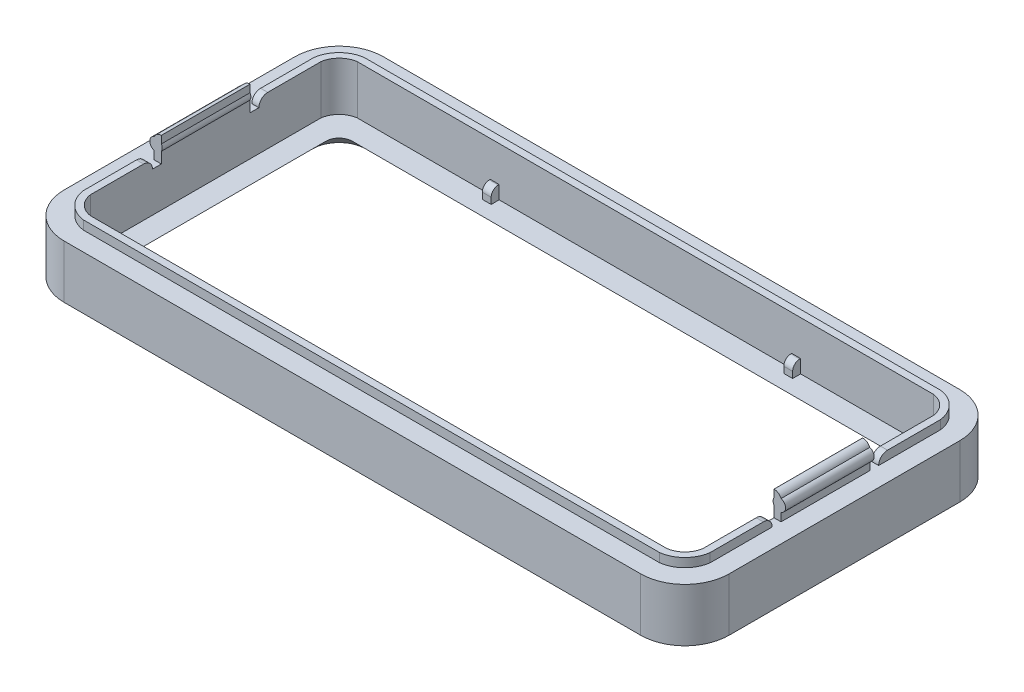
SolidWorks part; units mm, degrees
ref_plane "前视基准面" through (0, 0, 0) normal (0, 0, 1) x (1, 0, 0)
ref_plane "上视基准面" through (0, 0, 0) normal (0, 1, 0) x (1, 0, 0)
ref_plane "右视基准面" through (0, 0, 0) normal (1, 0, 0) x (0, 0, -1)
sketch "zero" plane through (0, 0, 0) normal (0, 1, 0) x (1, 0, 0)
  line L1 (-29.5, 15) -> (29.5, 15)
  line L2 (-32.5, 12) -> (-32.5, -12)
  line L3 (-29.5, -15) -> (29.5, -15)
  line L4 (32.5, 12) -> (32.5, -12)
  line L5 (-32.5, 15) -> (32.5, -15) construction
  line L6 (-32.5, -15) -> (32.5, 15) construction
  line L7 (-25.7, -15) -> (-14.5, -15)
  line L8 (-25.7, -15) -> (-25.7, -9.6569)
  line L9 (-25.7, -9.6569) -> (-14.5, -9.6569)
  line L10 (-14.5, -15) -> (-14.5, -9.6569)
  line L11 (5.2, -15) -> (12.7, -15)
  line L12 (5.2, -15) -> (5.2, -11)
  line L13 (5.2, -11) -> (12.7, -11)
  line L14 (12.7, -15) -> (12.7, -11)
  line L15 (17.8, -15) -> (25.3, -15)
  line L16 (17.8, -15) -> (17.8, -11)
  line L17 (17.8, -11) -> (25.3, -11)
  line L18 (25.3, -15) -> (25.3, -11)
  line L19 (-32.5, 7.7) -> (-19.5, 7.7)
  line L20 (-32.5, 7.7) -> (-32.5, -4.3)
  line L21 (-32.5, -4.3) -> (-19.5, -4.3)
  line L22 (-19.5, 7.7) -> (-19.5, -4.3)
  line L23 (-25.5, 14) -> (25.5, 14)
  line L24 (-25.5, 14) -> (-25.5, 8.8)
  line L25 (-25.5, 8.8) -> (25.5, 8.8)
  line L26 (25.5, 14) -> (25.5, 8.8)
  line L27 (-19.5, 7.2329) -> (-35.5, 7.2329)
  line L28 (-19.5, 7.2329) -> (-19.5, -3.7671)
  line L29 (-19.5, -3.7671) -> (-35.5, -3.7671)
  line L30 (-35.5, 7.2329) -> (-35.5, -3.7671)
  arc A0 (29.5, -15) -> (32.5, -12) centre (29.5, -12) ccw
  arc A1 (29.5, 15) -> (32.5, 12) centre (29.5, 12) cw
  arc A2 (-32.5, -12) -> (-29.5, -15) centre (-29.5, -12) ccw
  arc A3 (-29.5, 15) -> (-32.5, 12) centre (-29.5, 12) ccw
  circle A4 centre (-29, 11.4) radius 3
  circle A5 centre (-29, -11.5) radius 3
  circle A6 centre (29, 11.4) radius 3
  circle A7 centre (29, -11.5) radius 3
  circle A8 centre (-29, 11.4) radius 1.375
  circle A9 centre (-29, -11.5) radius 1.375
  circle A10 centre (29, -11.5) radius 1.375
  circle A11 centre (29, 11.4) radius 1.375
  point P0 (0, 0)
  dimension "D3" = 3
  dimension "D4" = 6
  dimension "D9" = 2.75
  dimension "D1" = 65
  dimension "D2" = 30
  dimension "D5" = 3.6
  dimension "D6" = 3.5
  dimension "D7" = 3.5
  dimension "D8" = 3.5
  dimension "D10" = 12
  dimension "D11" = 7.3
  dimension "D12" = 13
  dimension "D13" = 11.2
  dimension "D14" = 6.8
  dimension "D15" = 19.7
  dimension "D16" = 7.5
  dimension "D17" = 7.5
  dimension "D18" = 5.1
  dimension "D19" = 4
  dimension "D20" = 5.2
  dimension "D21" = 7
  dimension "D22" = 7
  dimension "D23" = 1
  dimension "D24" = 11
  dimension "D25" = 16
sketch "sugar" plane through (0, 0, 0) normal (0, 1, 0) x (1, 0, 0)
  line L1 (-29.5, 15) -> (29.5, 15)
  line L2 (-32.5, 12) -> (-32.5, -12)
  line L3 (-29.5, -15) -> (29.5, -15)
  line L4 (32.5, 12) -> (32.5, -12)
  line L5 (-32.5, 15) -> (32.5, -15) construction
  line L6 (-32.5, -15) -> (32.5, 15) construction
  line L7 (23.5, -11.5) -> (19.5, -11.5)
  line L8 (23.5, -11.5) -> (23.5, -13.9082)
  line L9 (23.5, -13.9082) -> (19.5, -13.9082)
  line L10 (19.5, -11.5) -> (19.5, -13.9082)
  line L11 (16, -11.0071) -> (8.5, -11.0071)
  line L12 (16, -11.0071) -> (16, -15)
  line L13 (16, -15) -> (8.5, -15)
  line L14 (8.5, -11.0071) -> (8.5, -15)
  line L15 (20.5, -13.9082) -> (22.5, -13.9082)
  line L16 (20.5, -13.9082) -> (20.5, -14.8173)
  line L17 (20.5, -14.8173) -> (22.5, -14.8173)
  line L18 (22.5, -13.9082) -> (22.5, -14.8173)
  arc A0 (29.5, 15) -> (32.5, 12) centre (29.5, 12) cw
  arc A1 (29.5, -15) -> (32.5, -12) centre (29.5, -12) ccw
  arc A2 (-32.5, -12) -> (-29.5, -15) centre (-29.5, -12) ccw
  arc A3 (-29.5, 15) -> (-32.5, 12) centre (-29.5, 12) ccw
  circle A4 centre (-29, 11.4) radius 3
  circle A5 centre (-29, 11.4) radius 1.375
  circle A6 centre (-29, -11.5) radius 3
  circle A7 centre (-29, -11.5) radius 1.375
  circle A8 centre (29, 11.4) radius 3
  circle A9 centre (29, 11.4) radius 1.375
  circle A10 centre (29, -11.5) radius 3
  circle A11 centre (29, -11.5) radius 1.375
  dimension "D3" = 3
  dimension "D1" = 65
  dimension "D2" = 30
  dimension "D4" = 9
  dimension "D5" = 4
  dimension "D6" = 3.5
  dimension "D7" = 7.5
  dimension "D8" = 2
  dimension "D9" = 1
sketch "case" plane through (0, 0, 0) normal (0, 1, 0) x (1, 0, 0)
  line L1 (-34.0422, 18) -> (30.9578, 18)
  line L2 (-39.0422, 13) -> (-39.0422, -13)
  line L3 (-34.0422, -18) -> (30.9578, -18)
  line L4 (35.9578, 13) -> (35.9578, -13)
  line L5 (-39.0422, 18) -> (35.9578, -18) construction
  line L6 (-39.0422, -18) -> (35.9578, 18) construction
  arc A0 (-39.0422, -13) -> (-34.0422, -18) centre (-34.0422, -13) ccw
  arc A1 (30.9578, -18) -> (35.9578, -13) centre (30.9578, -13) ccw
  arc A2 (30.9578, 18) -> (35.9578, 13) centre (30.9578, 13) cw
  arc A3 (-34.0422, 18) -> (-39.0422, 13) centre (-34.0422, 13) ccw
  point P0 (-1.5422, 0)
  point P3 (-1.5422, 0)
  dimension "D3" = 5
  dimension "D1" = 75
  dimension "D2" = 36
extrude "凸台-拉伸2" add sketch "case" along normal blind 6
sketch "草图2" plane through (0, 0, 0) normal (0, 1, 0) x (1, 0, 0)
  line L4 (-34.0422, -15.05) -> (30.9578, -15.05)
  line L5 (33.0078, -13) -> (33.0078, 13)
  line L6 (30.9578, 15.05) -> (-34.0422, 15.05)
  line L7 (-36.0922, 13) -> (-36.0922, -13)
  line L12 (33.8078, -13) -> (33.8078, 13)
  line L13 (30.9578, 15.85) -> (-34.0422, 15.85)
  line L14 (-36.8922, 13) -> (-36.8922, -13)
  line L15 (-34.0422, -15.85) -> (30.9578, -15.85)
  arc A4 (30.9578, -15.05) -> (33.0078, -13) centre (30.6303, -12.6725) ccw
  arc A5 (33.0078, 13) -> (30.9578, 15.05) centre (30.6303, 12.6725) ccw
  arc A6 (-34.0422, 15.05) -> (-36.0922, 13) centre (-33.7147, 12.6725) ccw
  arc A7 (-36.0922, -13) -> (-34.0422, -15.05) centre (-33.7147, -12.6725) ccw
  arc A12 (30.9578, -15.85) -> (33.8078, -13) centre (30.535, -12.5772) ccw
  arc A13 (33.8078, 13) -> (30.9578, 15.85) centre (30.535, 12.5772) ccw
  arc A14 (-34.0422, 15.85) -> (-36.8922, 13) centre (-33.6194, 12.5772) ccw
  arc A15 (-36.8922, -13) -> (-34.0422, -15.85) centre (-33.6194, -12.5772) ccw
ref_plane "基准面1" through (0, 6, 0) normal (0, 1, 0) x (1, 0, 0)
sketch "草图3" plane through (0, 6, 0) normal (0, 1, 0) x (1, 0, 0)
  line L4 (-34.0422, -15.05) -> (30.9578, -15.05)
  line L5 (33.0078, -13) -> (33.0078, 13)
  line L6 (30.9578, 15.05) -> (-34.0422, 15.05)
  line L7 (-36.0922, 13) -> (-36.0922, -13)
  line L8 (-34.0422, -15.05) -> (30.9578, -15.05)
  line L9 (33.0078, -13) -> (33.0078, 13)
  line L10 (30.9578, 15.05) -> (-34.0422, 15.05)
  line L11 (-36.0922, 13) -> (-36.0922, -13)
  line L12 (-36.8922, 13) -> (-36.8922, -13)
  line L13 (-34.0422, -15.85) -> (30.9578, -15.85)
  line L14 (33.8078, -13) -> (33.8078, 13)
  line L15 (30.9578, 15.85) -> (-34.0422, 15.85)
  line L16 (-36.8922, 13) -> (-36.8922, -13)
  line L17 (-34.0422, -15.85) -> (30.9578, -15.85)
  line L18 (33.8078, -13) -> (33.8078, 13)
  line L19 (30.9578, 15.85) -> (-34.0422, 15.85)
  arc A4 (30.9578, -15.05) -> (33.0078, -13) centre (30.6303, -12.6725) ccw
  arc A5 (33.0078, 13) -> (30.9578, 15.05) centre (30.6303, 12.6725) ccw
  arc A6 (-34.0422, 15.05) -> (-36.0922, 13) centre (-33.7147, 12.6725) ccw
  arc A7 (-36.0922, -13) -> (-34.0422, -15.05) centre (-33.7147, -12.6725) ccw
  arc A8 (30.9578, -15.05) -> (33.0078, -13) centre (30.6303, -12.6725) ccw
  arc A9 (33.0078, 13) -> (30.9578, 15.05) centre (30.6303, 12.6725) ccw
  arc A10 (-34.0422, 15.05) -> (-36.0922, 13) centre (-33.7147, 12.6725) ccw
  arc A11 (-36.0922, -13) -> (-34.0422, -15.05) centre (-33.7147, -12.6725) ccw
  arc A12 (-36.8922, -13) -> (-34.0422, -15.85) centre (-33.6194, -12.5772) ccw
  arc A13 (30.9578, -15.85) -> (33.8078, -13) centre (30.535, -12.5772) ccw
  arc A14 (33.8078, 13) -> (30.9578, 15.85) centre (30.535, 12.5772) ccw
  arc A15 (-34.0422, 15.85) -> (-36.8922, 13) centre (-33.6194, 12.5772) ccw
  arc A16 (-36.8922, -13) -> (-34.0422, -15.85) centre (-33.6194, -12.5772) ccw
  arc A17 (30.9578, -15.85) -> (33.8078, -13) centre (30.535, -12.5772) ccw
  arc A18 (33.8078, 13) -> (30.9578, 15.85) centre (30.535, 12.5772) ccw
  arc A19 (-34.0422, 15.85) -> (-36.8922, 13) centre (-33.6194, 12.5772) ccw
  dimension "D1" = 0
  dimension "D2" = 0
extrude "凸台-拉伸4" add sketch "草图3" along normal blind 1
ref_plane "基准面3" through (33.8078, 0, 0) normal (1, 0, 0) x (0, 0, -1)
sketch "草图7" plane through (0, 6, 0) normal (0, 1, 0) x (1, 0, 0)
  line L0 (-36.8922, 13) -> (-36.8922, -13) construction
  line L1 (-36.8922, 5) -> (-36.0922, 5)
  line L2 (-36.8922, 5) -> (-36.8922, -5)
  line L3 (-36.8922, -5) -> (-36.0922, -5)
  line L4 (-36.0922, 5) -> (-36.0922, -5)
  line L5 (-36.0922, 13) -> (-36.0922, -13) construction
  point P10 (-36.0922, 0)
  dimension "D1" = 5
  dimension "D2" = 10
extrude "凸台-拉伸8" add sketch "草图7" along normal blind 2.8
ref_plane "基准面5" through (0, 0, 5) normal (0, 0, 1) x (1, 0, 0)
sketch "草图8" plane through (0, 0, 5) normal (0, 0, 1) x (1, 0, 0)
  line L0 (-34.0422, 6) -> (-39.0422, 6) construction
  line L1 (-36.8922, 8.8) -> (-36.8922, 7) construction
  circle A0 centre (-36.6922, 7.6) radius 0.7
  dimension "D1" = 1.4
  dimension "D2" = 1.6
  dimension "D3" = 0.2
extrude "凸台-拉伸9" add sketch "草图8" against normal blind 10
fillet "圆角1" radius 0.85 1 edges at (-36.8922, 8.8, 0)
ref_plane "基准面7" through (-36.8922, 0, 0) normal (-1, 0, 0) x (0, 0, 1)
sketch "草图11" plane through (-36.8922, 0, 0) normal (-1, 0, 0) x (0, 0, 1)
  line L0 (-13, 6) -> (13, 6) construction
  line L1 (5, 7) -> (6, 7)
  line L2 (5, 7) -> (5, 6)
  line L3 (5, 6) -> (6, 6)
  line L4 (6, 7) -> (6, 6)
  line L6 (-5, 7) -> (-6, 7)
  line L7 (-5, 7) -> (-5, 6)
  line L8 (-5, 6) -> (-6, 6)
  line L9 (-6, 7) -> (-6, 6)
  dimension "D1" = 1
  dimension "D2" = 1
extrude "切除-拉伸1" cut sketch "草图11" against normal blind 1.2
fillet "圆角2" radius 1 2 edges at (-36.4922, 7, 6) (-36.4922, 7, -6)
ref_plane "基准面8" through (0, 0, 0) normal (0, -1, 0) x (-1, 0, 0)
sketch "草图13" plane through (0, 7, 0) normal (0, 1, 0) x (1, 0, 0)
  line L0 (33.0078, -13) -> (33.0078, 13) construction
  line L1 (33.0078, 5) -> (33.8078, 5)
  line L2 (33.0078, 5) -> (33.0078, -5)
  line L3 (33.0078, -5) -> (33.8078, -5)
  line L4 (33.8078, 5) -> (33.8078, -5)
  line L5 (33.8078, -13) -> (33.8078, 13) construction
  line L7 (35.9578, -13) -> (35.9578, 13) construction
  point P12 (35.9578, 0)
  point P13 (33.8078, 0)
  dimension "D1" = 10
extrude "凸台-拉伸10" add sketch "草图13" along normal blind 1.8
sketch "草图14" plane through (0, 0, 5) normal (0, 0, 1) x (1, 0, 0)
  line L0 (33.8078, 6) -> (30.9578, 6) construction
  line L1 (33.8078, 8.8) -> (33.8078, 7) construction
  circle A0 centre (33.6078, 7.6) radius 0.7
  dimension "D2" = 1.4
  dimension "D1" = 1.6
  dimension "D3" = 0.2
extrude "凸台-拉伸11" add sketch "草图14" against normal blind 10
fillet "圆角3" radius 0.85 1 edges at (33.8078, 8.8, 0)
sketch "草图15" plane through (0, 7, 0) normal (0, 1, 0) x (1, 0, 0)
  line L0 (33.8078, 5) -> (33.8078, 13) construction
  line L1 (33.0078, 5) -> (33.8078, 5)
  line L2 (33.0078, 5) -> (33.0078, 6)
  line L3 (33.0078, 6) -> (33.8078, 6)
  line L4 (33.8078, 5) -> (33.8078, 6)
  line L5 (33.8078, -13) -> (33.8078, -5) construction
  line L6 (33.0078, -5) -> (33.8078, -5)
  line L7 (33.0078, -5) -> (33.0078, -6)
  line L8 (33.0078, -6) -> (33.8078, -6)
  line L9 (33.8078, -5) -> (33.8078, -6)
  dimension "D1" = 1
  dimension "D2" = 1
extrude "切除-拉伸3" cut sketch "草图15" against normal blind 1
fillet "圆角4" radius 1 2 edges at (33.4078, 7, 6) (33.4078, 7, -6)
sketch "草图16" plane through (0, 6, 0) normal (0, 1, 0) x (1, 0, 0)
  line L4 (-34.0422, -15.05) -> (30.9578, -15.05)
  line L5 (33.0078, -13) -> (33.0078, 13)
  line L6 (30.9578, 15.05) -> (-34.0422, 15.05)
  line L7 (-36.0922, 13) -> (-36.0922, -13)
  line L8 (-34.0422, -15.05) -> (30.9578, -15.05)
  line L9 (33.0078, -13) -> (33.0078, 13)
  line L10 (30.9578, 15.05) -> (-34.0422, 15.05)
  line L11 (-36.0922, 13) -> (-36.0922, -13)
  arc A4 (30.9578, -15.05) -> (33.0078, -13) centre (30.6303, -12.6725) ccw
  arc A5 (33.0078, 13) -> (30.9578, 15.05) centre (30.6303, 12.6725) ccw
  arc A6 (-34.0422, 15.05) -> (-36.0922, 13) centre (-33.7147, 12.6725) ccw
  arc A7 (-36.0922, -13) -> (-34.0422, -15.05) centre (-33.7147, -12.6725) ccw
  arc A8 (30.9578, -15.05) -> (33.0078, -13) centre (30.6303, -12.6725) ccw
  arc A9 (33.0078, 13) -> (30.9578, 15.05) centre (30.6303, 12.6725) ccw
  arc A10 (-34.0422, 15.05) -> (-36.0922, 13) centre (-33.7147, 12.6725) ccw
  arc A11 (-36.0922, -13) -> (-34.0422, -15.05) centre (-33.7147, -12.6725) ccw
  dimension "D1" = 0
extrude "切除-拉伸4" cut sketch "草图16" against normal blind 4.5
sketch "草图17" plane through (0, 1.5, 0) normal (0, 1, 0) x (1, 0, 0)
  line L0 (30.9578, 18) -> (-34.0422, 18) construction
  line L1 (-33.5422, 12.5) -> (30.4578, 12.5)
  line L2 (-33.5422, 12.5) -> (-33.5422, -12.5)
  line L3 (-33.5422, -12.5) -> (30.4578, -12.5)
  line L4 (30.4578, 12.5) -> (30.4578, -12.5)
  line L5 (-39.0422, 13) -> (-39.0422, -13) construction
  point P4 (-1.5422, 12.5)
  point P7 (-1.5422, 18)
  point P8 (-33.5422, 0)
  point P11 (-39.0422, 0)
  dimension "D1" = 25
  dimension "D2" = 64
extrude "切除-拉伸5" cut sketch "草图17" against normal blind 1.5
fillet "圆角5" radius 1.5 4 edges at (30.4578, 0.75, 12.5) (30.4578, 0.75, -12.5) (-33.5422, 0.75, -12.5) (-33.5422, 0.75, 12.5)
sketch "草图20" plane through (0, 1.5, 0) normal (0, 1, 0) x (1, 0, 0)
  line L0 (30.9578, 15.05) -> (-34.0422, 15.05) construction
  line L1 (-19.0422, 15.05) -> (-18.0422, 15.05)
  line L2 (-19.0422, 15.05) -> (-19.0422, 14.15)
  line L3 (-19.0422, 14.15) -> (-18.0422, 14.15)
  line L4 (-18.0422, 15.05) -> (-18.0422, 14.15)
  line L6 (-34.0422, -15.05) -> (30.9578, -15.05) construction
  line L7 (15.9578, 15.05) -> (14.9578, 15.05)
  line L8 (15.9578, 15.05) -> (15.9578, 14.15)
  line L9 (15.9578, 14.15) -> (14.9578, 14.15)
  line L10 (14.9578, 15.05) -> (14.9578, 14.15)
  line L11 (-19.0422, -15.05) -> (-18.0422, -15.05)
  line L12 (-19.0422, -15.05) -> (-19.0422, -14.15)
  line L13 (-19.0422, -14.15) -> (-18.0422, -14.15)
  line L14 (-18.0422, -15.05) -> (-18.0422, -14.15)
  line L15 (-39.0422, 13) -> (-39.0422, -13) construction
  line L16 (14.9578, -15.05) -> (15.9578, -15.05)
  line L17 (14.9578, -15.05) -> (14.9578, -14.15)
  line L18 (14.9578, -14.15) -> (15.9578, -14.15)
  line L19 (15.9578, -15.05) -> (15.9578, -14.15)
  line L21 (35.9578, -13) -> (35.9578, 13) construction
  dimension "D1" = 20
  dimension "D2" = 20
  dimension "D3" = 1
  dimension "D4" = 1
  dimension "D5" = 20
  dimension "D6" = 20
  dimension "D7" = 1
  dimension "D8" = 1
  dimension "D9" = 0.9
  dimension "D10" = 0.9
  dimension "D11" = 0.9
  dimension "D12" = 0.9
extrude "凸台-拉伸14" add sketch "草图20" along normal blind 1.5
fillet "圆角8" radius 0.8 4 edges at (15.4578, 3, 14.15) (-18.5422, 3, 14.15) (15.4578, 3, -14.15) (-18.5422, 3, -14.15)
chamfer "倒角3" distance 1.5 angle 45 8 edges at (-1.5422, 0, -12.5) (-33.1029, 0, -12.0607) (30.0185, 0, -12.0607) (-33.5422, 0, 0) (30.4578, 0, 0) (-33.1029, 0, 12.0607) (30.0185, 0, 12.0607) (-1.5422, 0, 12.5)
